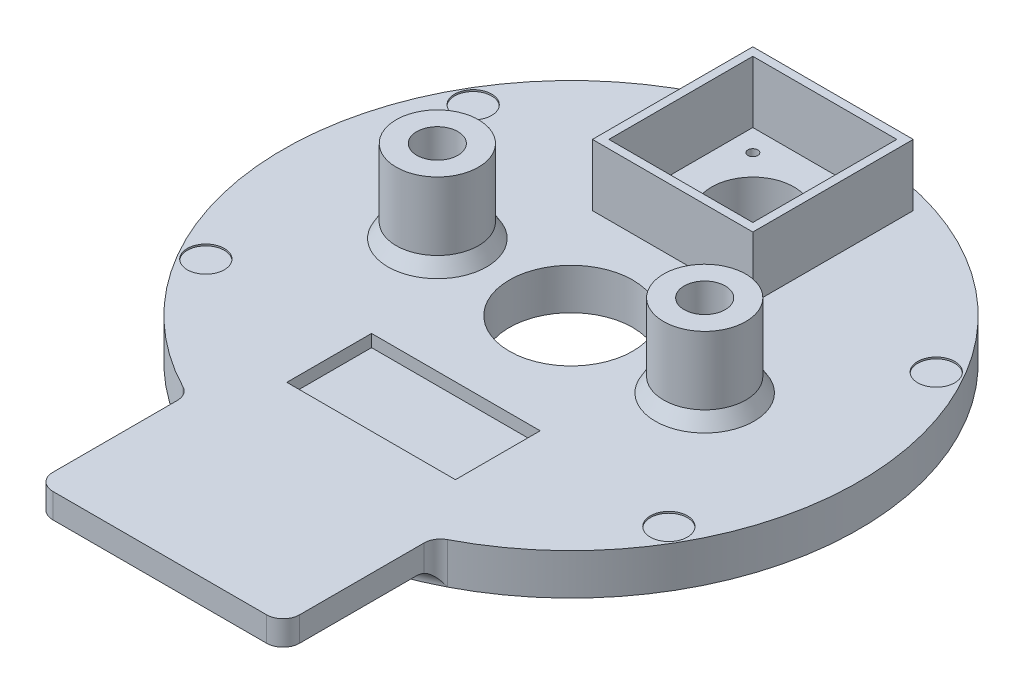
SolidWorks part; units mm, degrees
ref_plane "Front Plane" through (0, 0, 0) normal (0, 0, 1) x (1, 0, 0)
ref_plane "Top Plane" through (0, 0, 0) normal (0, 1, 0) x (1, 0, 0)
ref_plane "Right Plane" through (0, 0, 0) normal (1, 0, 0) x (0, 0, -1)
sketch "Sketch1" plane through (0, 0, 0) normal (0, 1, 0) x (1, 0, 0)
  circle A0 centre (0, 0) radius 88.9
  dimension "6" = 177.8
extrude "Boss-Extrude1" add sketch "Sketch1" along normal blind 12.7
sketch "Sketch9" plane through (0, 12.7, 0) normal (0, 1, 0) x (1, 0, 0)
  line L5 (-24.765, 80.899) -> (-24.765, 31.369)
  line L7 (-22.225, 78.359) -> (22.225, 78.359)
  line L9 (-22.225, 78.359) -> (-22.225, 33.909)
  line L10 (0, 56.134) -> (0, 0) construction
  line L11 (-22.225, 33.909) -> (22.225, 33.909)
  line L37 (22.225, 78.359) -> (22.225, 33.909)
  line L38 (-22.225, 78.359) -> (22.225, 33.909) construction
  line L39 (-22.225, 33.909) -> (22.225, 78.359) construction
  line L40 (-24.765, 31.369) -> (24.765, 31.369)
  line L41 (24.765, 80.899) -> (24.765, 31.369)
  line L42 (-24.765, 80.899) -> (24.765, 80.899)
  dimension "D1" = 44.45
  dimension "D2" = 44.45
  dimension "D3" = 56.134
  dimension "D4" = 2.54
extrude "Boss-Extrude2" add sketch "Sketch9" along normal blind 19.05
sketch "Sketch10" plane through (0, 12.7, 0) normal (0, 1, 0) x (1, 0, 0)
  line L1 (71.4904, 41.275) -> (-71.4904, 41.275) construction
  line L2 (71.4904, 41.275) -> (71.4904, -41.275) construction
  line L3 (71.4904, -41.275) -> (-71.4904, -41.275) construction
  line L4 (-71.4904, 41.275) -> (-71.4904, -41.275) construction
  line L5 (71.4904, 41.275) -> (-71.4904, -41.275) construction
  line L6 (71.4904, -41.275) -> (-71.4904, 41.275) construction
  circle A0 centre (0, 0) radius 82.55 construction
  circle A1 centre (-71.4904, -41.275) radius 5.715
  circle A2 centre (-71.4904, 41.275) radius 5.715
  circle A3 centre (71.4904, 41.275) radius 5.715
  circle A4 centre (71.4904, -41.275) radius 5.715
  point P0 (0, 0)
  dimension "D1" = 165.1
  dimension "D3" = 11.43
  dimension "D2" = 30
extrude "Cut-Extrude7" cut sketch "Sketch10" against normal blind 0.508
sketch "Sketch12" [suppressed] plane through (0, 7.62, 0) normal (0, 1, 0) x (1, 0, 0)
  circle A0 centre (-58.3726, 48.9804) radius 1.5
  circle A1 centre (58.3726, 48.9804) radius 1.5
  circle A2 centre (-58.3726, -48.9804) radius 1.5
  circle A3 centre (58.3726, -48.9804) radius 1.5
  dimension "D1" = 3
extrude "Cut-Extrude9" [suppressed] cut sketch "Sketch12" against normal up to surface (7.62 mm away) up to face at (0, 0, 88.9)
sketch "Sketch13" [suppressed] plane through (0, 0, 0) normal (0, -1, 0) x (1, 0, 0)
  circle A1 centre (-58.3726, 48.9804) radius 1.905
  circle A2 centre (-58.3726, 48.9804) radius 1.905
  circle A3 centre (58.3726, 48.9804) radius 1.905
  circle A4 centre (58.3726, 48.9804) radius 1.905
  circle A5 centre (58.3726, -48.9804) radius 1.905
  circle A6 centre (58.3726, -48.9804) radius 1.905
  circle A7 centre (-58.3726, -48.9804) radius 1.905
  circle A8 centre (-58.3726, -48.9804) radius 1.905
  dimension "D1" = 0
  dimension "D2" = 0
  dimension "D3" = 0
  dimension "D4" = 0
extrude "Cut-Extrude10" [suppressed] cut sketch "Sketch13" against normal blind 12.7
sketch "Sketch14" plane through (0, 0, 0) normal (0, -1, 0) x (1, 0, 0)
  circle A0 centre (0, 0) radius 19.05
  dimension "D1" = 38.1
extrude "Cut-Extrude11" cut sketch "Sketch14" against normal up to surface (12.7 mm away) up to face at (71.4904, 12.7, 46.99)
sketch "Sketch15" plane through (0, 12.7, 0) normal (0, 1, 0) x (1, 0, 0)
  line L0 (-41.275, 0) -> (41.275, 0) construction
  circle A0 centre (41.275, 0) radius 6.35
  circle A1 centre (-41.275, 0) radius 6.35
  circle A2 centre (-41.275, 0) radius 12.7
  circle A3 centre (41.275, 0) radius 12.7
  dimension "D1" = 6.35
  dimension "D2" = 82.55
  dimension "D3" = 12.7
extrude "Boss-Extrude3" add sketch "Sketch15" along normal blind 25.4
sketch "Sketch16" plane through (0, 12.7, 0) normal (0, 1, 0) x (1, 0, 0)
  circle A0 centre (41.275, 0) radius 6.35 construction
  circle A1 centre (-41.275, 0) radius 6.35 construction
  circle A2 centre (41.275, 0) radius 6.35
  circle A3 centre (-41.275, 0) radius 6.35
extrude "Cut-Extrude12" cut sketch "Sketch16" against normal blind 12.7
sketch "Sketch17" plane through (0, 0, 0) normal (0, -1, 0) x (1, 0, 0)
  circle A0 centre (41.275, 0) radius 9.525
  circle A1 centre (-41.275, 0) radius 9.525
  dimension "D1" = 19.05
  dimension "D2" = 19.05
extrude "Cut-Extrude13" cut sketch "Sketch17" against normal blind 25.4
sketch "Sketch18" plane through (0, 12.7, 0) normal (0, 1, 0) x (1, 0, 0)
  circle A1 centre (0, 0) radius 19.05 construction
  circle A2 centre (0, 0) radius 19.05
  circle A3 centre (0, 0) radius 24.13
  dimension "D1" = 5.08
extrude "Boss-Extrude4" [suppressed] add sketch "Sketch18" along normal blind 6.35
chamfer "Chamfer2" distance 2.54 angle 60 2 edges at (41.275, 12.7, 12.7) (-41.275, 12.7, 12.7) first distance on face at (41.275, 12.7, 12.7)
sketch "Sketch19" plane through (0, 12.7, 0) normal (0, 1, 0) x (1, 0, 0)
  line L0 (22.225, 56.134) -> (-22.225, 56.134) construction
  line L1 (22.225, 33.909) -> (22.225, 78.359) construction
  line L2 (0, 88.9) -> (0, 0) construction
  line L4 (-22.225, 78.359) -> (-22.225, 33.909) construction
  line L5 (-15.494, 71.628) -> (15.494, 71.628) construction
  line L6 (-15.494, 71.628) -> (-15.494, 40.64) construction
  line L7 (-15.494, 40.64) -> (15.494, 40.64) construction
  line L8 (15.494, 71.628) -> (15.494, 40.64) construction
  line L9 (-15.494, 71.628) -> (15.494, 40.64) construction
  line L10 (-15.494, 40.64) -> (15.494, 71.628) construction
  circle A0 centre (0, 56.134) radius 12.7
  circle A1 centre (15.494, 71.628) radius 1.524
  circle A2 centre (15.494, 40.64) radius 1.524
  circle A3 centre (-15.494, 40.64) radius 1.524
  circle A4 centre (-15.494, 71.628) radius 1.524
  circle A5 centre (0, 0) radius 88.9 construction
  dimension "D2" = 25.4
  dimension "D5" = 3.048
  dimension "D3" = 30.988
  dimension "D4" = 30.988
extrude "Cut-Extrude14" cut sketch "Sketch19" against normal up to surface (12.7 mm away) up to face at (41.275, 0, -9.525)
sketch "Sketch20" [suppressed] plane through (0, 12.7, 0) normal (0, 1, 0) x (1, 0, 0)
  circle A0 centre (-71.4904, -41.275) radius 4.191 construction
  circle A1 centre (71.4904, -41.275) radius 4.191 construction
  circle A2 centre (71.4904, 41.275) radius 4.191 construction
  circle A3 centre (-71.4904, 41.275) radius 4.191 construction
  circle A4 centre (-71.4904, -41.275) radius 4.191
  circle A5 centre (71.4904, -41.275) radius 4.191
  circle A6 centre (71.4904, 41.275) radius 4.191
  circle A7 centre (-71.4904, 41.275) radius 4.191
  circle A8 centre (-71.4904, 41.275) radius 5.461
  circle A9 centre (71.4904, 41.275) radius 5.461
  circle A10 centre (71.4904, -41.275) radius 5.461
  circle A11 centre (-71.4904, -41.275) radius 5.461
  dimension "D1" = 1.27
fillet "Fillet1" [suppressed] radius 6.35
sketch "Sketch21" plane through (0, 0, 0) normal (0, -1, 0) x (1, 0, 0)
  circle A0 centre (-15.494, -71.628) radius 1.524 construction
  circle A1 centre (15.494, -71.628) radius 1.524 construction
  circle A2 centre (15.494, -40.64) radius 1.524 construction
  circle A3 centre (-15.494, -40.64) radius 1.524 construction
  circle A4 centre (-15.494, -71.628) radius 1.524 construction
  circle A5 centre (15.494, -71.628) radius 1.524 construction
  circle A6 centre (15.494, -40.64) radius 1.524 construction
  circle A7 centre (-15.494, -40.64) radius 1.524 construction
  circle A8 centre (-15.494, -71.628) radius 4.064
  circle A9 centre (15.494, -71.628) radius 4.064
  circle A10 centre (15.494, -40.64) radius 4.064
  circle A11 centre (-15.494, -40.64) radius 4.064
  circle A12 centre (-71.4904, 41.275) radius 5.715 construction
  circle A13 centre (-71.4904, 41.275) radius 5.715
  circle A14 centre (71.4904, 41.275) radius 5.715 construction
  circle A15 centre (71.4904, 41.275) radius 5.715
  circle A16 centre (71.4904, -41.275) radius 5.715 construction
  circle A17 centre (71.4904, -41.275) radius 5.715
  circle A18 centre (-71.4904, -41.275) radius 5.715 construction
  circle A19 centre (-71.4904, -41.275) radius 5.715
  dimension "D1" = 2.54
extrude "Cut-Extrude15" cut sketch "Sketch21" against normal blind 5.08
ref_plane "Plane1" through (0, 12.7, 0) normal (0, 1, 0) x (1, 0, 0)
sketch "Sketch22" plane through (0, 12.7, 0) normal (0, 1, 0) x (1, 0, 0)
  line L0 (0, -19.05) -> (0, -88.9) construction
  line L2 (-26.035, -35.56) -> (26.035, -35.56)
  line L3 (-26.035, -35.56) -> (-26.035, -61.722)
  line L4 (-26.035, -61.722) -> (26.035, -61.722)
  line L5 (26.035, -35.56) -> (26.035, -61.722)
  line L6 (-26.035, -35.56) -> (26.035, -61.722) construction
  line L7 (-26.035, -61.722) -> (26.035, -35.56) construction
  circle A0 centre (0, 0) radius 19.05 construction
  circle A1 centre (0, 0) radius 88.9 construction
  point P7 (0, -48.641)
  dimension "D1" = 52.07
  dimension "D2" = 26.162
  dimension "D3" = 35.56
extrude "Cut-Extrude17" cut sketch "Sketch22" against normal blind 3.81
sketch "Sketch23" plane through (0, 12.7, 0) normal (0, 1, 0) x (1, 0, 0)
  line L0 (0, 0) -> (0, -88.9) construction
  line L1 (-38.1, -80.3219) -> (-38.1, -127)
  line L2 (-38.1, -127) -> (38.1, -127)
  line L3 (38.1, -80.3219) -> (38.1, -127)
  circle A0 centre (0, 0) radius 88.9 construction
  arc A1 (-38.1, -80.3219) -> (38.1, -80.3219) centre (0, 0) ccw
  point P13 (0, -127)
  dimension "D1" = 38.1
  dimension "D2" = 38.1
extrude "Boss-Extrude5" add sketch "Sketch23" against normal blind 7.62
fillet "Fillet2" radius 5.08 5 edges at (38.1, 8.89, 127) (-38.1, 8.89, 127) (-38.1, 8.89, 80.3219) (0, 5.08, 88.9) (38.1, 8.89, 80.3219)
equation "\"25nn\"=0.497491"
